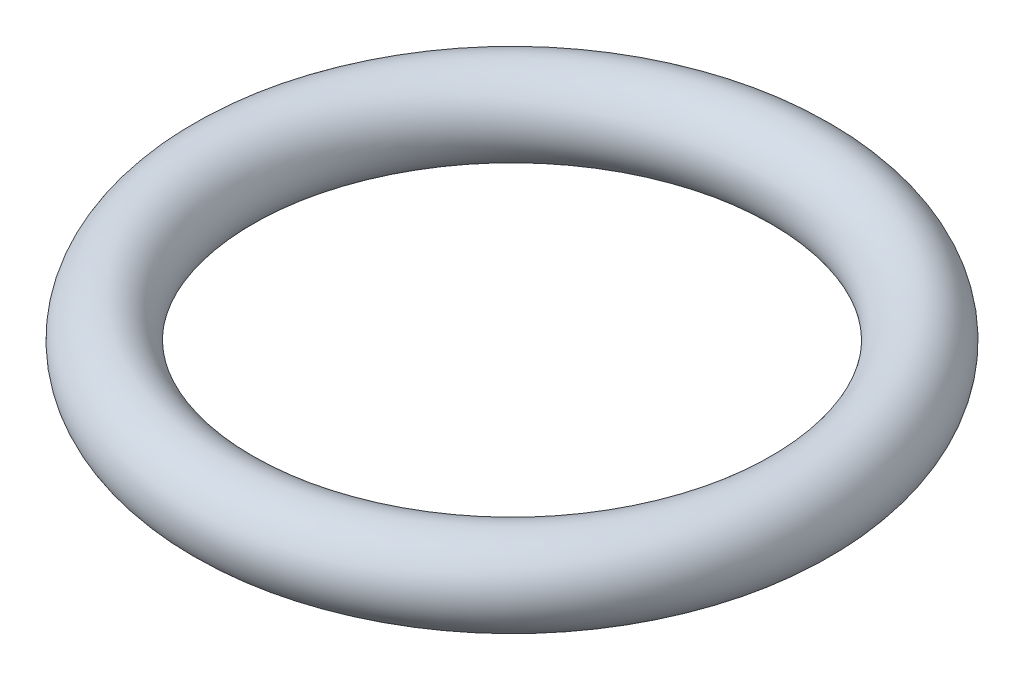
SolidWorks part; units mm, degrees
ref_plane "Front Plane" through (0, 0, 0) normal (0, 0, 1) x (1, 0, 0)
ref_plane "Top Plane" through (0, 0, 0) normal (0, 1, 0) x (1, 0, 0)
ref_plane "Right Plane" through (0, 0, 0) normal (1, 0, 0) x (0, 0, -1)
sketch "Sketch2" plane through (0, 0, 0) normal (0, 0, 1) x (1, 0, 0)
  line L0 (0, 0) -> (0, 3.8497) construction
  circle A0 centre (5.25, 0) radius 0.75
  dimension "D1" = 1.5
  dimension "D2" = 5.25
revolve "Revolve1" add sketch "Sketch2" angle 360 about L0
sketch "Sketch3" plane through (0, 0, 0) normal (0, 1, 0) x (1, 0, 0)
  circle A0 centre (0, 0) radius 5.25 construction
  dimension "D1" = 10.5
